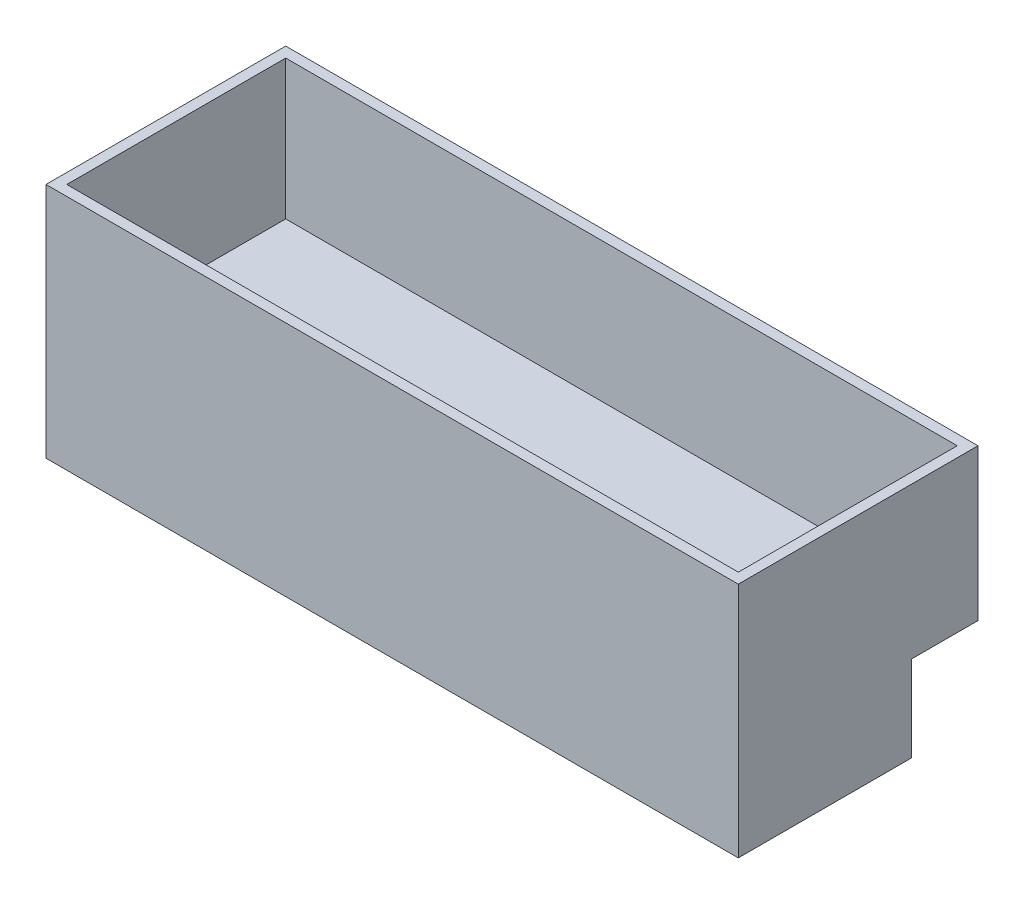
SolidWorks part; units mm, degrees
ref_plane "Ebene vorne" through (0, 0, 0) normal (0, 0, 1) x (1, 0, 0)
ref_plane "Ebene oben" through (0, 0, 0) normal (0, 1, 0) x (1, 0, 0)
ref_plane "Ebene rechts" through (0, 0, 0) normal (1, 0, 0) x (0, 0, -1)
sketch "Skizze1" plane through (0, 0, 0) normal (0, 1, 0) x (1, 0, 0)
  line L1 (-382.6289, 137.1473) -> (417.3711, 137.1473)
  line L2 (-382.6289, 137.1473) -> (-382.6289, -62.8527)
  line L3 (-382.6289, -62.8527) -> (417.3711, -62.8527)
  line L4 (417.3711, 137.1473) -> (417.3711, -62.8527)
  dimension "D1" = 800
  dimension "D2" = 200
extrude "Aufsatz-Linear austragen1" add sketch "Skizze1" along normal blind 274
sketch "Skizze2" plane through (0, 0, 0) normal (0, -1, 0) x (-1, 0, 0)
  line L0 (347.6289, -47.8527) -> (347.6289, 122.1473)
  line L1 (347.6289, 122.1473) -> (332.6289, 122.1473)
  line L2 (332.6289, 122.1473) -> (332.6289, -47.8527)
  line L3 (332.6289, -47.8527) -> (347.6289, -47.8527)
  line L4 (-337.3711, -47.8527) -> (-337.3711, 122.1473)
  line L5 (-337.3711, 122.1473) -> (-352.3711, 122.1473)
  line L6 (-352.3711, 122.1473) -> (-352.3711, -47.8527)
  line L7 (-352.3711, -47.8527) -> (-337.3711, -47.8527)
  line L8 (382.6289, 137.1473) -> (382.6289, -62.8527) construction
  line L10 (-417.3711, -62.8527) -> (-417.3711, 137.1473) construction
  point P6 (347.6289, 37.1473)
  point P11 (382.6289, 37.1473)
  point P12 (-352.3711, 37.1473)
  point P15 (-417.3711, 37.1473)
  dimension "D1" = 170
  dimension "D2" = 15
  dimension "D3" = 35
  dimension "D4" = 700
extrude "Aufsatz-Linear austragen2" add sketch "Skizze2" along normal blind 6
sketch "Skizze4" plane through (0, 0, -137.1473) normal (0, 0, -1) x (-1, 0, 0)
  line L0 (382.6289, 274) -> (382.6289, 0) construction
  line L1 (-417.3711, 274) -> (382.6289, 274)
  line L2 (-417.3711, 274) -> (-417.3711, 99)
  line L3 (-417.3711, 99) -> (382.6289, 99)
  line L4 (382.6289, 274) -> (382.6289, 99)
  dimension "D1" = 175
extrude "Aufsatz-Linear austragen3" add sketch "Skizze4" along normal blind 77
sketch "Skizze5" plane through (0, 274, 0) normal (0, 1, 0) x (1, 0, 0)
  line L0 (417.3711, -62.8527) -> (417.3711, 214.1473) construction
  line L1 (-370.6289, -50.8527) -> (405.3711, -50.8527)
  line L2 (-370.6289, -50.8527) -> (-370.6289, 202.1473)
  line L3 (-370.6289, 202.1473) -> (405.3711, 202.1473)
  line L4 (405.3711, -50.8527) -> (405.3711, 202.1473)
  line L5 (-382.6289, 214.1473) -> (417.3711, 214.1473) construction
  line L6 (-382.6289, -62.8527) -> (417.3711, -62.8527) construction
  line L7 (-382.6289, 214.1473) -> (-382.6289, -62.8527) construction
  dimension "D1" = 12
  dimension "D2" = 12
  dimension "D3" = 12
  dimension "D4" = 12
extrude "Schnitt-Linear austragen2" cut sketch "Skizze5" against normal blind 161
